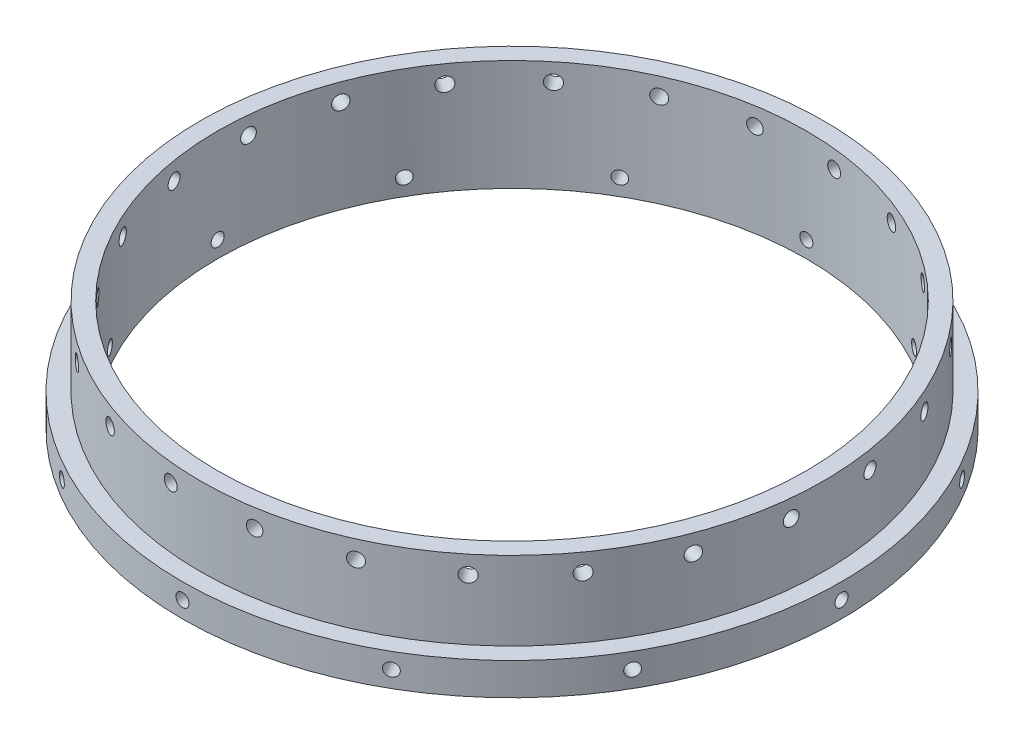
SolidWorks part; units mm, degrees
ref_plane "Front Plane" through (0, 0, 0) normal (0, 0, 1) x (1, 0, 0)
ref_plane "Top Plane" through (0, 0, 0) normal (0, 1, 0) x (1, 0, 0)
ref_plane "Right Plane" through (0, 0, 0) normal (1, 0, 0) x (0, 0, -1)
sketch "Sketch1" plane through (0, 0, 0) normal (0, 1, 0) x (1, 0, 0)
  circle A0 centre (0, 0) radius 75.565
  circle A1 centre (0, 0) radius 67.501
  dimension "D1" = 135.002
  dimension "D2" = 151.13
extrude "Boss-Extrude1" add sketch "Sketch1" along normal blind 25.4
hole_wizard "Tap Drill for M4x0.7 Tap1" positions "3DSketch1" profile "Sketch2" hole size "M4x0.7" standard "ANSI Metric" end condition up to next
sketch3d "3DSketch1"
  point P0 (31.0779, 21.2994, 68.8784)
sketch "Sketch2" plane through (31.0779, 21.2994, 68.8784) normal (0, 1, 0) x (0.9115, 0, -0.4113)
  line L0 (0, 0) -> (0, 153.0736)
  line L1 (0, 153.0736) -> (1.65, 153.0736)
  line L2 (1.65, 153.0736) -> (1.65, 0)
  line L5 (1.65, 0) -> (0, 0)
  line L11 (0, -6.35) -> (0, 107.95) construction
  dimension "Thru Hole Dia." = 3.3
  dimension "Thru Hole Depth" = 153.0736
pattern_circular "CirPattern1" count 24 every 15 about axis through (0, 25.4, 0) along (0, 1, 0) of "Tap Drill for M4x0.7 Tap1"
sketch "Sketch4" plane through (0, 0, 0) normal (1, 0, 0) x (0, 0, -1)
  line L0 (0, 0) -> (0, 3.7846) construction
  circle A0 centre (0, 3.7846) radius 1.5
extrude "Cut-Extrude1" cut sketch "Sketch4" against normal blind 113.03
pattern_circular "CirPattern2" count 12 every 30 about axis through (0, 0, 0) along (0, 1, 0) of "Cut-Extrude1"
sketch "Sketch7" plane through (0, 25.4, 0) normal (0, 1, 0) x (1, 0, 0)
  circle A0 centre (0, 0) radius 71.501
  circle A1 centre (0, 0) radius 75.565
  dimension "D1" = 143.002
extrude "Cut-Extrude2" cut sketch "Sketch7" against normal blind 18
